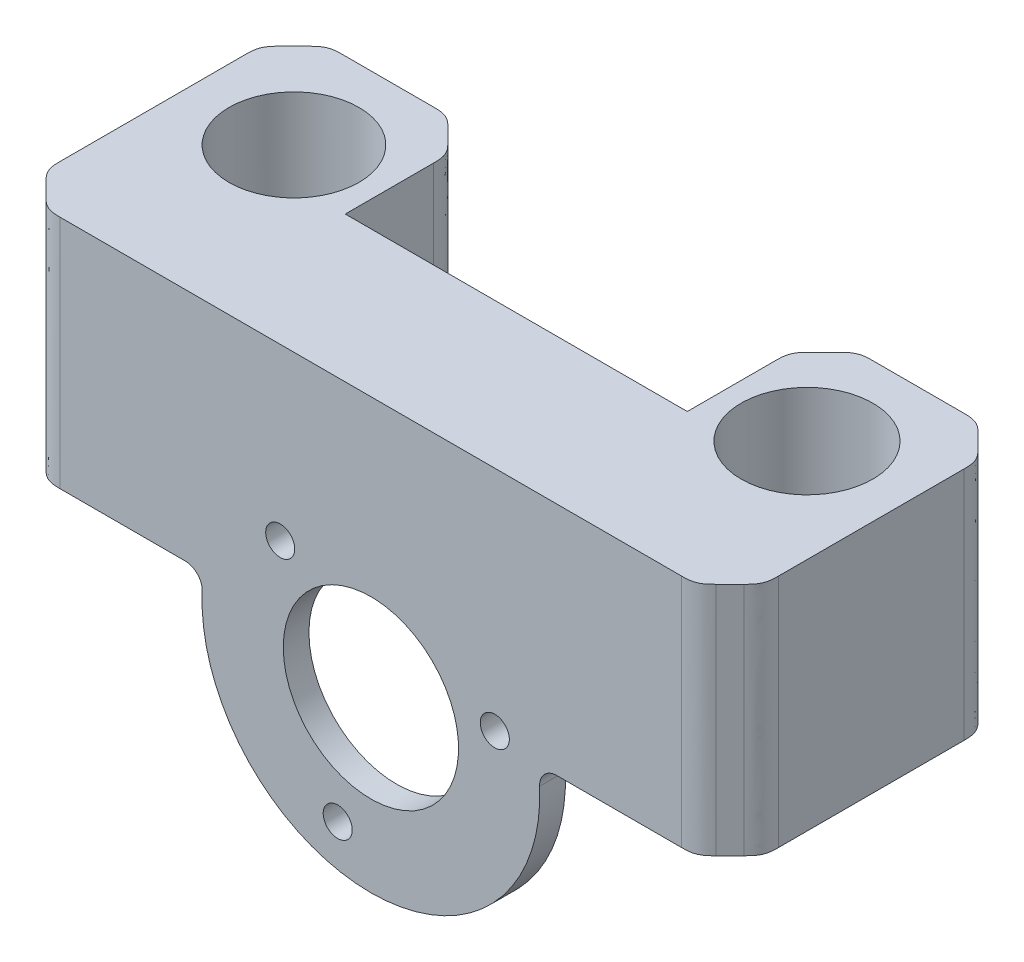
SolidWorks part; units mm, degrees
ref_plane "Plan de face" through (0, 0, 0) normal (0, 0, 1) x (1, 0, 0)
ref_plane "Plan de dessus" through (0, 0, 0) normal (0, 1, 0) x (1, 0, 0)
ref_plane "Plan de droite" through (0, 0, 0) normal (1, 0, 0) x (0, 0, -1)
sketch "Esquisse1" plane through (0, 0, 0) normal (0, 1, 0) x (1, 0, 0)
  line L1 (-26, -21) -> (26, -21)
  line L2 (0, 0) -> (0, -4) construction
  line L3 (17, -4) -> (-17, -4)
  line L4 (-20, 8) -> (-20, 12) construction
  line L5 (-20, 12) -> (-24, 12) construction
  line L6 (-24, 12) -> (-20, 8)
  line L7 (-24, 12) -> (-38, 12)
  line L8 (-38, 8) -> (-38, 12) construction
  line L9 (-38, 8) -> (-42, 8) construction
  line L10 (-42, 8) -> (-38, 12)
  line L11 (-42, 8) -> (-42, 0)
  line L12 (-20, 1) -> (-20, -4) construction
  line L17 (-42, 0) -> (-30, 0) construction
  line L18 (-42, 0) -> (-42, -17)
  line L19 (-42, -17) -> (-38, -17) construction
  line L20 (-38, -17) -> (-38, -21) construction
  line L21 (-42, -17) -> (-38, -21)
  line L22 (-38, -21) -> (-26, -21)
  line L24 (0, -21) -> (0, -4) construction
  line L25 (-30, 0) -> (0, 0) construction
  line L26 (0, -55) -> (0, 55) construction
  line L27 (38, -17) -> (38, -21) construction
  line L28 (42, -17) -> (38, -17) construction
  line L29 (42, 0) -> (30, 0) construction
  line L30 (20, -4) -> (17, -4) construction
  line L31 (20, -4) -> (20, 1) construction
  line L32 (38, 8) -> (42, 8) construction
  line L33 (38, 8) -> (38, 12) construction
  line L34 (20, 12) -> (24, 12) construction
  line L35 (20, 8) -> (20, 12) construction
  line L45 (-20, 1) -> (-20, 8)
  line L46 (20, 1) -> (20, 8)
  line L47 (38, -21) -> (26, -21)
  line L48 (42, -17) -> (38, -21)
  line L49 (42, 0) -> (42, -17)
  line L51 (42, 8) -> (42, 0)
  line L52 (42, 8) -> (38, 12)
  line L53 (24, 12) -> (38, 12)
  line L54 (24, 12) -> (20, 8)
  line L56 (-20, -4) -> (-17, -4) construction
  line L57 (20, 1) -> (20, -4)
  line L58 (20, -4) -> (17, -4)
  line L59 (-20, 1) -> (-20, -4)
  line L60 (-20, -4) -> (-17, -4)
  circle A0 centre (-30, 0) radius 7.6
  circle A2 centre (30, 0) radius 7.6
  dimension "D3" = 15.2
  dimension "D4" = 4
  dimension "D15" = 30
  dimension "D2" = 4
  dimension "D5" = 4
  dimension "D6" = 4
  dimension "D7" = 17
  dimension "D8" = 3
  dimension "D9" = 8
  dimension "D10" = 17
  dimension "D11" = 4
  dimension "D12" = 4
  dimension "D13" = 12
  dimension "D14" = 5
extrude "Boss.-Extru.1" add sketch "Esquisse1" along normal blind 25
sketch "Esquisse3" plane through (0, 0, 0) normal (0, -1, 0) x (1, 0, 0)
  line L0 (30, 0) -> (-30, 0) construction
  line L1 (0, -55) -> (0, 55) construction
  circle A0 centre (-30, 0) radius 7.6
  circle A1 centre (-30, 0) radius 4.4
  circle A2 centre (30, 0) radius 4.4
  circle A3 centre (30, 0) radius 7.6
  point P8 (0, 0)
  dimension "D2" = 15.2
  dimension "D3" = 8.8
  dimension "D1" = 30
extrude "Boss.-Extru.3" add sketch "Esquisse3" along normal blind 2.5 separate body
extrude "Boss.-Extru.5" add sketch "Esquisse1<4>" against normal blind 2.5
sketch "Esquisse1<4>" plane through (0, 0, 0) normal (0, 1, 0) x (1, 0, 0) same geometry as "Esquisse1"
fillet "Congé1" radius 4 12 edges at (-42, 11.25, 17) (-42, 11.25, -8) (-38, 11.25, -12) (-24, 11.25, -12) (-38, 11.25, 21) (-20, 11.25, -8) (38, 11.25, 21) (42, 11.25, 17) (42, 11.25, -8) (38, 11.25, -12) (24, 11.25, -12) (20, 11.25, -8) curvature continuous yes
sketch "Esquisse7" plane through (0, 0, 4) normal (0, 0, -1) x (-1, 0, 0)
  line L0 (0, 9.5) -> (0, -5.5) construction
  line L1 (-20, 25) -> (20, 25) construction
  line L2 (0, -5.5) -> (-3.6235, 8.023) construction
  line L3 (0, 9.5) -> (0, 25) construction
  line L4 (0, -5.5) -> (3.8823, -19.9889) construction
  line L5 (0, -5.5) -> (-14.4889, -1.6177) construction
  line L6 (0, -5.5) -> (10.6066, 5.1066) construction
  line L7 (0, -5.5) -> (-9.8995, -15.3995) construction
  line L8 (0, -5.5) -> (13.523, -9.1235) construction
  circle A0 centre (0, -5.5) radius 19.75
  circle A1 centre (0, -5.5) radius 15 construction
  circle A2 centre (-14.4889, -1.6177) radius 1.7
  circle A3 centre (10.6066, 5.1066) radius 1.7
  circle A4 centre (3.8823, -19.9889) radius 1.7
  circle A5 centre (0, -5.5) radius 10.25
  circle A6 centre (0, -5.5) radius 14 construction
  circle A7 centre (-3.6235, 8.023) radius 1.7 construction
  circle A8 centre (-9.8995, -15.3995) radius 1.7
  circle A9 centre (13.523, -9.1235) radius 1.7 construction
  line M4 (-20, -2.5) -> (20, -2.5)
  dimension "D2" = 39.5
  dimension "D3" = 30
  dimension "D6" = 15
  dimension "D7" = 3.4
  dimension "D8" = 20.5
  dimension "D10" = 28
  dimension "D11" = 15
  dimension "D1" = 15.5
  dimension "D4" = 120
  dimension "D5" = 120
  dimension "D9" = 45
  dimension "D12" = 120
  dimension "D13" = 120
extrude "Enlèv. mat.-Extru.1" cut sketch "Esquisse7" against normal blind 14 contours A0 A3 A2 M4 region at (-0.0292, 5.7486, 4)
sketch "Esquisse10" plane through (0, 0, 21) normal (0, 0, 1) x (1, 0, 0)
  line L0 (-36.3431, -2.5) -> (36.3431, -2.5) construction
  line L1 (19.5208, -2.5) -> (-19.5208, -2.5)
  arc A0 (-19.5208, -2.5) -> (19.5208, -2.5) centre (0, -5.5) ccw
extrude "Boss.-Extru.9" add sketch "Esquisse10" against normal blind 3
extrude "Enlèv. mat.-Extru.2" cut sketch "Esquisse7<4>" against normal through all contours A4 | A2 | A3 | A5 M4 | A5 M4 | A2 region at (0, 0.511, 4) region at (0, -8.2818, 4) region at (14.4889, -1.3412, 4) region at (-10.6066, 5.1066, 4) region at (-3.8823, -19.9889, 4)
sketch "Esquisse7<4>" plane through (0, 0, 4) normal (0, 0, -1) x (-1, 0, 0) same geometry as "Esquisse7"
sketch "Esquisse11" plane through (0, 25, 0) normal (0, 1, 0) x (1, 0, 0)
  circle A0 centre (-30, 0) radius 7.6
  circle A1 centre (30, 0) radius 7.7
  dimension "D1" = 15.2
extrude "Enlèv. mat.-Extru.3" cut sketch "Esquisse11" against normal blind 24
fillet "Congé2" radius 2 2 edges at (-19.5208, -2.5, 19.5) (19.5208, -2.5, 19.5)
